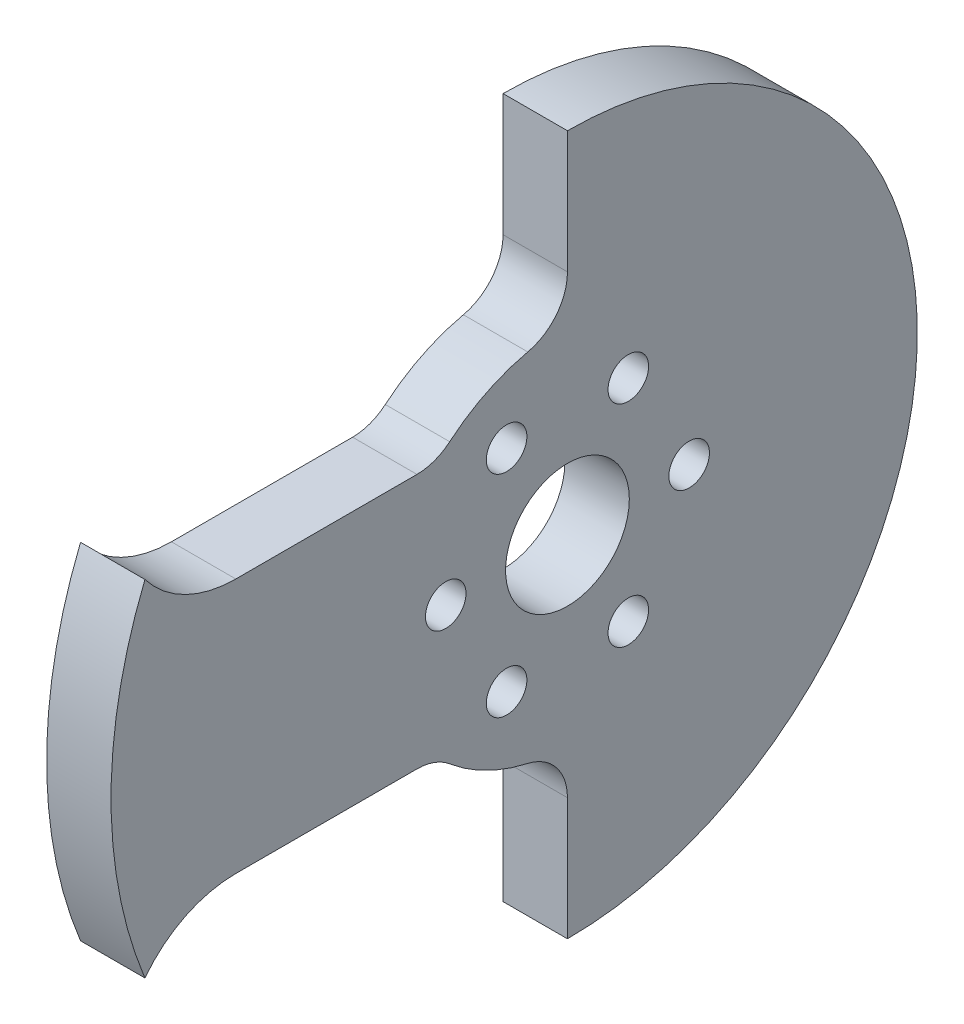
SolidWorks part; units mm, degrees
material "Alloy Steel"
ref_plane "Front Plane" through (0, 0, 0) normal (0, 0, 1) x (1, 0, 0)
ref_plane "Top Plane" through (0, 0, 0) normal (0, 1, 0) x (1, 0, 0)
ref_plane "Right Plane" through (0, 0, 0) normal (1, 0, 0) x (0, 0, -1)
other "Center of Mass"
sketch "Sketch1" plane through (0, 0, 0) normal (1, 0, 0) x (0, 0, -1)
  line L0 (23.5692, 47) -> (-3.4308, 47) construction
  line L1 (53.5692, 47) -> (47.5692, 57.3923) construction
  line L2 (47.5692, 57.3923) -> (35.5692, 57.3923) construction
  line L3 (35.5692, 57.3923) -> (29.5692, 47) construction
  line L4 (29.5692, 47) -> (35.5692, 36.6077) construction
  line L5 (35.5692, 36.6077) -> (47.5692, 36.6077) construction
  line L6 (47.5692, 36.6077) -> (53.5692, 47) construction
  line L7 (-0.0899, 64.0152) -> (-0.0286, 63.9362)
  line L8 (-0.0899, 64.0152) -> (-0.1277, 63.9226) construction
  line L9 (8.8703, 59.575) -> (26.7328, 59.575)
  line L10 (8.8703, 34.425) -> (26.7328, 34.425)
  line L11 (-0.0899, 29.9848) -> (-0.0286, 30.0638)
  line L12 (41.5692, 69.4499) -> (41.5692, 81.5)
  line L13 (41.5692, 24.5501) -> (41.5692, 12.5)
  line L14 (41.5692, -953) -> (41.5692, 49047) construction
  circle A0 centre (41.5692, 47) radius 45 construction
  circle A1 centre (41.5692, 47) radius 45 construction
  circle A2 centre (41.5692, 47) radius 6 construction
  circle A3 centre (41.5692, 47) radius 6.1
  circle A4 centre (41.5692, 47) radius 18 construction
  circle A5 centre (41.5692, 47) radius 10.3923 construction
  circle A6 centre (47.5692, 57.3923) radius 2
  circle A7 centre (47.5692, 57.3923) radius 6 construction
  circle A8 centre (35.5692, 57.3923) radius 2
  circle A9 centre (29.5692, 47) radius 2
  circle A10 centre (35.5692, 36.6077) radius 2
  circle A11 centre (47.5692, 36.6077) radius 2
  circle A12 centre (53.5692, 47) radius 2
  arc A13 (-0.0899, 64.0152) -> (-0.0899, 29.9848) centre (41.5692, 47) ccw
  arc A14 (-0.0286, 63.9362) -> (8.8703, 59.575) centre (8.8703, 70.8346) ccw
  arc A15 (26.7328, 59.575) -> (29.9581, 60.7543) centre (26.7328, 64.575) ccw
  arc A16 (26.7328, 34.425) -> (29.9581, 33.2457) centre (26.7328, 29.425) cw
  arc A17 (-0.0286, 30.0638) -> (8.8703, 34.425) centre (8.8703, 23.1654) cw
  circle A18 centre (41.5692, 47) radius 21.3961 construction
  circle A19 centre (41.5692, 47) radius 21.3961 construction
  arc A20 (41.5692, 81.5) -> (41.5692, 12.5) centre (41.5692, 47) cw
  arc A21 (41.5692, 69.4499) -> (37.6562, 64.5695) centre (36.5692, 69.4499) cw
  arc A22 (37.6562, 64.5695) -> (29.9581, 60.7543) centre (41.5692, 47) ccw
  arc A23 (37.6562, 29.4305) -> (29.9581, 33.2457) centre (41.5692, 47) cw
  arc A24 (41.5692, 24.5501) -> (37.6562, 29.4305) centre (36.5692, 24.5501) ccw
  point P39 (41.5692, 92)
  dimension "D1" = 12
  dimension "D2" = 0.1
  dimension "D3" = 4
  dimension "D4" = 24
  dimension "D9" = 5
  dimension "D10" = 34.5
  dimension "D5" = 0.1
  dimension "D6" = 60
  dimension "D7" = 25.15
  dimension "D8" = 10
  dimension "D11" = 10.5
extrude "Boss-Extrude1" add sketch "Sketch1" along normal blind 3.175 and the other way blind 3.175
ref_axis "Axis1" through (3.175, 47, -41.5692) along (-1, 0, 0)
